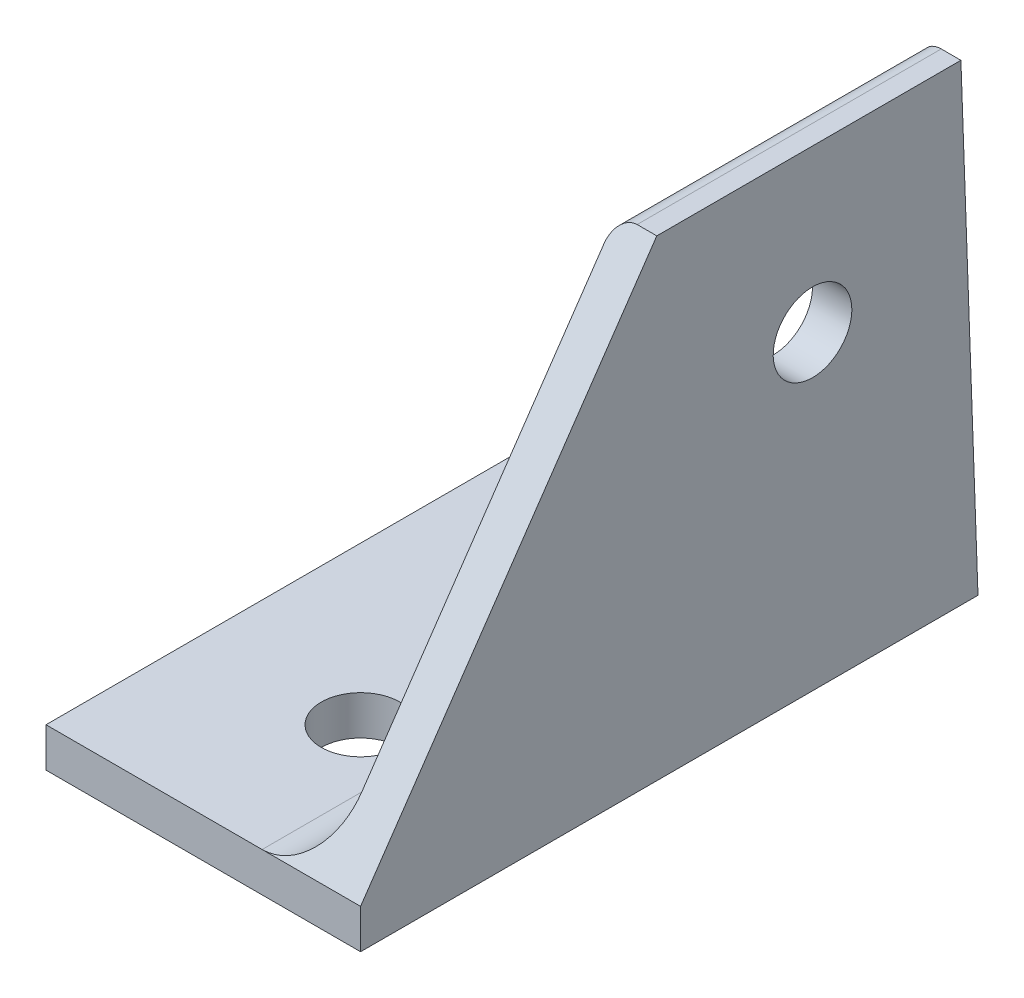
SolidWorks part; units mm, degrees
ref_plane "Front Plane" through (0, 0, 0) normal (0, 0, 1) x (1, 0, 0)
ref_plane "Top Plane" through (0, 0, 0) normal (0, 1, 0) x (1, 0, 0)
ref_plane "Right Plane" through (0, 0, 0) normal (1, 0, 0) x (0, 0, -1)
sketch "Sketch0" plane through (0, 0, 0) normal (0, 0, 1) x (1, 0, 0)
  line L0 (-19.05, -19.05) -> (19.05, -19.05)
  line L1 (19.05, -19.05) -> (19.05, 19.05)
  line L2 (19.05, 0) -> (0, 0) construction
  line L3 (0, 0) -> (0, -19.05) construction
  line L4 (15.875, -11.0998) -> (15.875, 19.05) construction
  line L5 (11.0998, -15.875) -> (-19.05, -15.875) construction
  arc A0 (15.875, -11.0998) -> (11.0998, -15.875) centre (11.0998, -11.0998) cw
  point P3 (14.4764, -14.4764)
  dimension "Inside Corner Radius" = 4.7752
  dimension "Outside Height" = 38.1
  dimension "Inside Height" = 34.925
  dimension "Inside Width" = 34.925
  dimension "Wall Thickness" = 3.175
  dimension "D1" = 3.175
  dimension "Outside Width" = 38.1
sketch "Sketch1" plane through (0, 0, 0) normal (1, 0, 0) x (0, 0, -1)
  line L0 (25.4, 0) -> (-25.4, 0)
  point P4 (0, 0)
  dimension "Length" = 50.8
sketch "Sketch2" plane through (0, 0, 0) normal (0, 0, 1) x (1, 0, 0)
  line L0 (-19.05, -19.05) -> (19.05, -19.05)
  line L1 (19.05, -19.05) -> (19.05, 19.05)
  line L2 (19.05, 19.05) -> (15.875, 19.05) construction
  line L3 (15.875, 17.4625) -> (15.875, -11.0998)
  line L4 (11.0998, -15.875) -> (-17.4625, -15.875)
  line L5 (-19.05, -19.05) -> (-19.05, -15.875) construction
  line L6 (17.4625, 19.05) -> (19.05, 19.05)
  line L7 (-19.05, -17.4625) -> (-19.05, -19.05)
  line L8 (19.05, 0) -> (0, 0) construction
  line L9 (0, 0) -> (0, -19.05) construction
  arc A0 (15.875, 17.4625) -> (17.4625, 19.05) centre (17.4625, 17.4625) cw
  arc A1 (-19.05, -17.4625) -> (-17.4625, -15.875) centre (-17.4625, -17.4625) cw
  arc A2 (15.875, -11.0998) -> (11.0998, -15.875) centre (11.0998, -11.0998) cw
  dimension "Inside Radius" = 4.7752
  dimension "Height" = 38.1
  dimension "Width" = 38.1
  dimension "Thickness" = 3.175
extrude "Boss-Extrude1" add sketch "Sketch2" along normal mid plane 50.8
sketch "Break Locations" plane through (0, 0, 0) normal (1, 0, 0) x (0, 0, -1)
  line L0 (13.462, 0) -> (-13.462, 0)
  line L1 (-25.4, -19.05) -> (-25.4, 19.05) construction
  line L2 (25.4, -19.05) -> (25.4, 19.05) construction
  point P0 (6.985, 0)
  point P1 (-6.985, 0)
  point P10 (0, 0)
  point P11 (-13.462, 0)
  point P13 (13.462, 0)
  dimension "D1" = 32.385
  dimension "D2" = 32.385
  dimension "D3" = 38.862
sketch "Sketch3" plane through (0, -19.05, 0) normal (0, -1, 0) x (1, 0, 0)
  line L0 (19.05, 25.4) -> (6.35, 25.4) construction
  line L1 (-19.05, 25.4) -> (19.05, 25.4) construction
  line L2 (6.35, 25.4) -> (6.35, 12.7) construction
  line L3 (6.35, 12.7) -> (6.35, -12.7) construction
  line L4 (-19.05, 25.4) -> (-6.35, 25.4)
  line L5 (-6.35, 25.4) -> (-6.35, -25.4)
  line L6 (-19.05, -25.4) -> (19.05, -25.4) construction
  line L7 (-6.35, -25.4) -> (-19.05, -25.4)
  line L8 (-19.05, -25.4) -> (-19.05, 25.4)
  circle A0 centre (6.35, 12.7) radius 3.175
  circle A1 centre (6.35, -12.7) radius 3.175
  dimension "D4" = 12.7
  dimension "D1" = 12.7
  dimension "D2" = 12.7
  dimension "D3" = 25.4
extrude "Cut-Extrude1" cut sketch "Sketch3" against normal through all
sketch "Sketch12" plane through (19.05, 0, 0) normal (1, 0, 0) x (0, 0, -1)
  line L0 (23.0694, 19.05) -> (24.4495, -19.05)
  line L1 (24.0478, -18.3158) -> (10.4507, 500.9362) construction
  line L2 (-25.4, 19.05) -> (25.4, 19.05) construction
  line L3 (-25.4, -19.05) -> (25.4, -19.05) construction
  line L5 (-1.4842, 19.05) -> (-25.4, -15.875)
  line L6 (-25.4, -19.05) -> (-25.4, 19.05) construction
  line L7 (-25.4, -15.875) -> (-25.4, -19.05)
  line L8 (-25.4, -19.05) -> (24.4495, -19.05)
  line L9 (23.0694, 19.05) -> (-1.4842, 19.05)
  dimension "D1" = 3.175
extrude "Cut-Extrude2" cut sketch "Sketch12" against normal through all flip side to cut
sketch "Sketch13" plane through (19.05, 0, 0) normal (1, 0, 0) x (0, 0, -1)
  line L0 (10.7562, 18.7176) -> (11.0886, 6.0219) construction
  circle A0 centre (11.0886, 6.0219) radius 3.175
extrude "Cut-Extrude3" cut sketch "Sketch13" against normal through all
sketch "Sketch14" plane through (0, -15.875, 0) normal (0, 1, 0) x (1, 0, 0)
  circle A0 centre (6.35, -12.7) radius 6.35
  circle A1 centre (6.35, 12.7) radius 6.35
extrude "Cut-Extrude4" cut sketch "Sketch14" along normal blind 2.54
equation "\"D1@Break Locations\" = .85 * \"Height@Sketch2\""
equation "\"D2@Break Locations\"=\"D1@Break Locations\""
equation "\"Thickness@Sketch2\"=\"wall thickness@sketch0\""
equation "\"Height@Sketch2\"=\"outside height@sketch0\""
equation "\"Width@Sketch2\"=\"outside width@sketch0\""
equation "\"Inside Radius@Sketch2\"=\"inside corner radius@sketch0\""
equation "\"Length@Boss-Extrude1\"=\"length@sketch1\""
equation "\"D3@Break Locations\"=\"D2@Break Locations\"*1.2"
equation "\"D1@Sketch0\"=\"Wall Thickness@Sketch0\""
